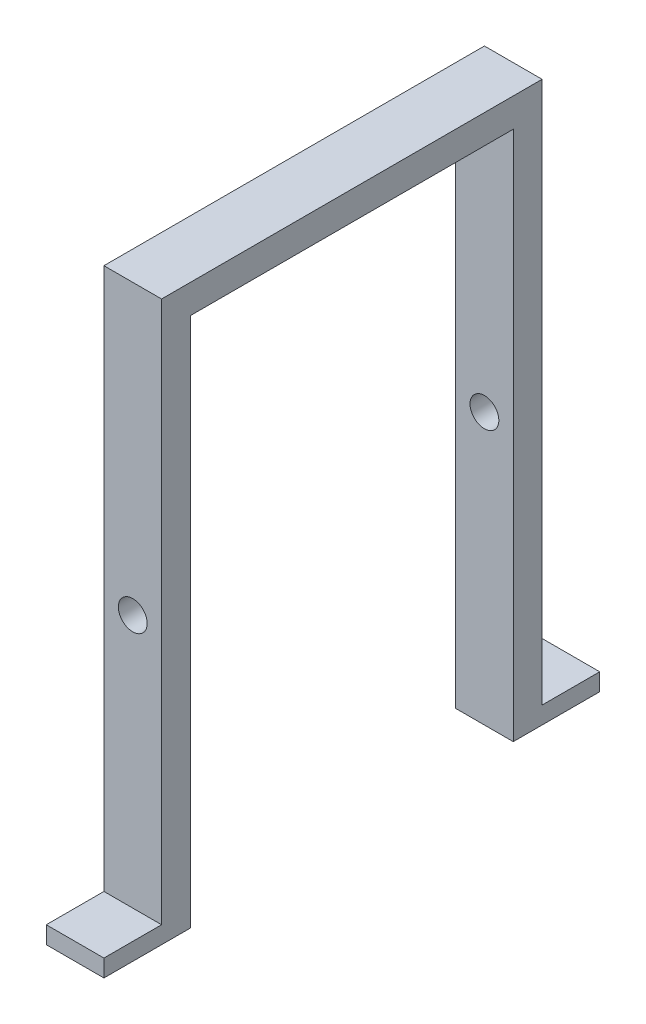
SolidWorks part; units mm, degrees
material "1060 Alloy"
ref_plane "Front Plane" through (0, 0, 0) normal (0, 0, 1) x (1, 0, 0)
ref_plane "Top Plane" through (0, 0, 0) normal (0, 1, 0) x (1, 0, 0)
ref_plane "Right Plane" through (0, 0, 0) normal (1, 0, 0) x (0, 0, -1)
sketch "Sketch1" plane through (0, 0, 0) normal (1, 0, 0) x (0, 0, -1)
  line L0 (-33, 3) -> (-33, 97)
  line L1 (-33, 97) -> (33, 97)
  line L2 (33, 97) -> (33, 3)
  line L3 (33, 0) -> (28, 0)
  line L4 (28, 0) -> (28, 92)
  line L5 (28, 92) -> (-28, 92)
  line L6 (-28, 92) -> (-28, 0)
  line L7 (-33, 0) -> (-28, 0)
  line L8 (-33, 47) -> (33, 47) construction
  line L9 (-33, 3) -> (-43, 3)
  line L10 (-43, 3) -> (-43, 0)
  line L11 (-43, 0) -> (-33, 0)
  line L12 (33, 3) -> (43, 3)
  line L13 (43, 3) -> (43, 0)
  line L14 (43, 0) -> (33, 0)
  line L15 (-28, 0) -> (28, 0) construction
  line L16 (-33, 0) -> (-33, 3) construction
  dimension "D1" = 47
  dimension "D2" = 5
  dimension "D3" = 56
  dimension "D4" = 15
  dimension "D5" = 3
  dimension "D6" = 5
  dimension "D7" = 50
extrude "Boss-Extrude1" add sketch "Sketch1" along normal blind 5 and the other way blind 5
sketch "Sketch2" plane through (0, 0, 33) normal (0, 0, 1) x (1, 0, 0)
  line L0 (0, 0) -> (0, 97) construction
  line L1 (-5, 97) -> (5, 97) construction
  circle A0 centre (0, 47) radius 2.5
  dimension "D2" = 47
extrude "Cut-Extrude1" cut sketch "Sketch2" against normal through all
equation "\"SpringOuterDiameter\"= 80"
equation "\"CarriageWidth\"=56"
equation "\"D3@Sketch1\"=\"CarriageWidth\""
equation "\"StrutWidth\"=15"
equation "\"D4@Sketch1\"=\"StrutWidth\""
equation "\"D1@Sketch1\"= \"SpringOuterDiameter\" / 2 + 2 + \"PulleyDiameter\" / 2 'extra 2mm for clearance above strut"
equation "\"D2@Sketch2\"= \"SpringOuterDiameter\" / 2 + 2 + \"PulleyDiameter\" / 2'extra 2mm for clearance above strut"
equation "\"D7@Sketch1\"= \"SpringOuterDiameter\" / 2 + 10'extra 10mm for easy hook on of the spring"
equation "\"PulleyDiameter\"= 10"
